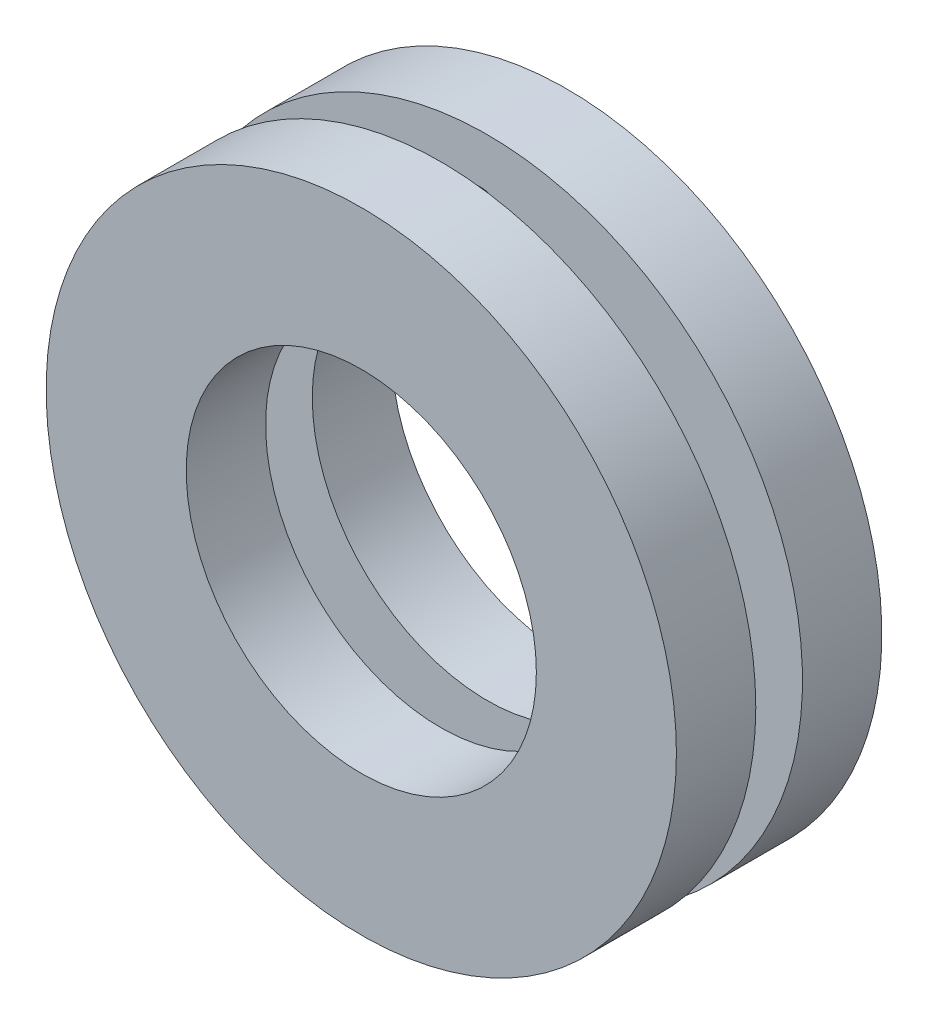
SolidWorks part; units mm, degrees
ref_plane "前视基准面" through (0, 0, 0) normal (0, 0, 1) x (1, 0, 0)
ref_plane "上视基准面" through (0, 0, 0) normal (0, 1, 0) x (1, 0, 0)
ref_plane "右视基准面" through (0, 0, 0) normal (1, 0, 0) x (0, 0, -1)
sketch "草图1" plane through (0, 0, 0) normal (0, 0, 1) x (1, 0, 0)
  circle A0 centre (0, 0) radius 67.5
  dimension "D1" = 135
extrude "拉伸1" add sketch "草图1" along normal blind 17
sketch "草图3" plane through (0, 0, 0) normal (1, 0, 0) x (0, 0, -1)
  line L0 (0, 55) -> (10, 55)
  line L1 (0, -67.5) -> (0, 67.5) construction
  arc A0 (10, 55) -> (0, 55) centre (5, 55) ccw
  dimension "D1" = 10
  dimension "D2" = 55
revolve "旋转1" add sketch "草图3" angle 360 about L0
ref_axis "基准轴1" through (0, 0, 17) along (0, 0, -1)
ref_plane "基准面1" through (0, 0, -10) normal (0, 0, -1) x (-1, 0, 0)
sketch "草图5" plane through (0, 0, -10) normal (0, 0, -1) x (-1, 0, 0)
  circle A0 centre (0, 0) radius 67.5
  circle A1 centre (0, 0) radius 37.5
  dimension "D1" = 135
  dimension "D2" = 75
extrude "拉伸2" add sketch "草图5" along normal blind 17
sketch "草图6" plane through (0, 0, 17) normal (0, 0, 1) x (1, 0, 0)
  circle A0 centre (0, 0) radius 37.5
  dimension "D1" = 75
extrude "切除-拉伸1" cut sketch "草图6" against normal blind 30
